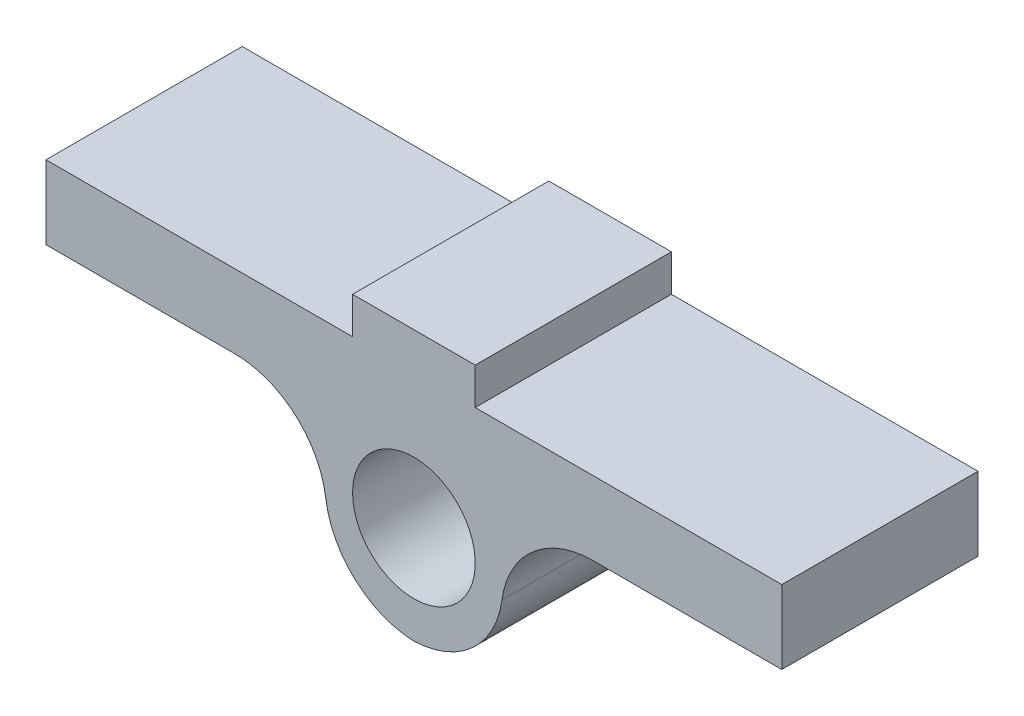
SolidWorks part; units mm, degrees
ref_plane "Front Plane" through (0, 0, 0) normal (0, 0, 1) x (1, 0, 0)
ref_plane "Top Plane" through (0, 0, 0) normal (0, 1, 0) x (1, 0, 0)
ref_plane "Right Plane" through (0, 0, 0) normal (1, 0, 0) x (0, 0, -1)
sketch "Sketch1" plane through (0, 0, 0) normal (0, 1, 0) x (1, 0, 0)
  line L1 (0, 0) -> (60, 0)
  line L2 (0, 0) -> (0, 16)
  line L3 (0, 16) -> (60, 16)
  line L4 (60, 0) -> (60, 16)
  dimension "D1" = 60
  dimension "D2" = 16
extrude "Boss-Extrude1" add sketch "Sketch1" along normal blind 6
sketch "Sketch2" plane through (0, 6, 0) normal (0, 1, 0) x (1, 0, 0)
  line L0 (60, 16) -> (0, 16) construction
  line L1 (25, 16) -> (35, 16)
  line L2 (25, 16) -> (25, 0)
  line L3 (25, 0) -> (35, 0)
  line L4 (35, 16) -> (35, 0)
  line L5 (0, 0) -> (60, 0) construction
  line L6 (0, 16) -> (0, 0) construction
  dimension "D1" = 10
  dimension "D2" = 25
extrude "Boss-Extrude2" add sketch "Sketch2" along normal blind 3
sketch "Sketch4" plane through (0, 0, 0) normal (0, -1, 0) x (1, 0, 0)
  line L0 (0, 0) -> (60, 0) construction
  line L1 (22.75, 0) -> (37.25, 0)
  line L2 (22.75, 0) -> (22.75, -16)
  line L3 (22.75, -16) -> (37.25, -16)
  line L4 (37.25, 0) -> (37.25, -16)
  line L5 (60, -16) -> (0, -16) construction
  line L6 (0, -16) -> (0, 0) construction
  dimension "D1" = 14.5
  dimension "D2" = 22.75
extrude "Boss-Extrude3" add sketch "Sketch4" along normal blind 13
sketch "Sketch5" plane through (0, 0, -16) normal (0, 0, -1) x (-1, 0, 0)
  line L0 (-37.25, -13) -> (-37.25, 0) construction
  line L1 (-22.75, -13) -> (-37.25, -13) construction
  circle A0 centre (-30, -5) radius 5
  dimension "D1" = 7.25
  dimension "D2" = 8
extrude "Cut-Extrude1" cut sketch "Sketch5" against normal through all
fillet "Fillet1" radius 7.5 2 edges at (22.75, -13, -8) (37.25, -13, -8)
fillet "Fillet2" radius 7.5 2 edges at (22.75, 0, -8) (37.25, 0, -8)
